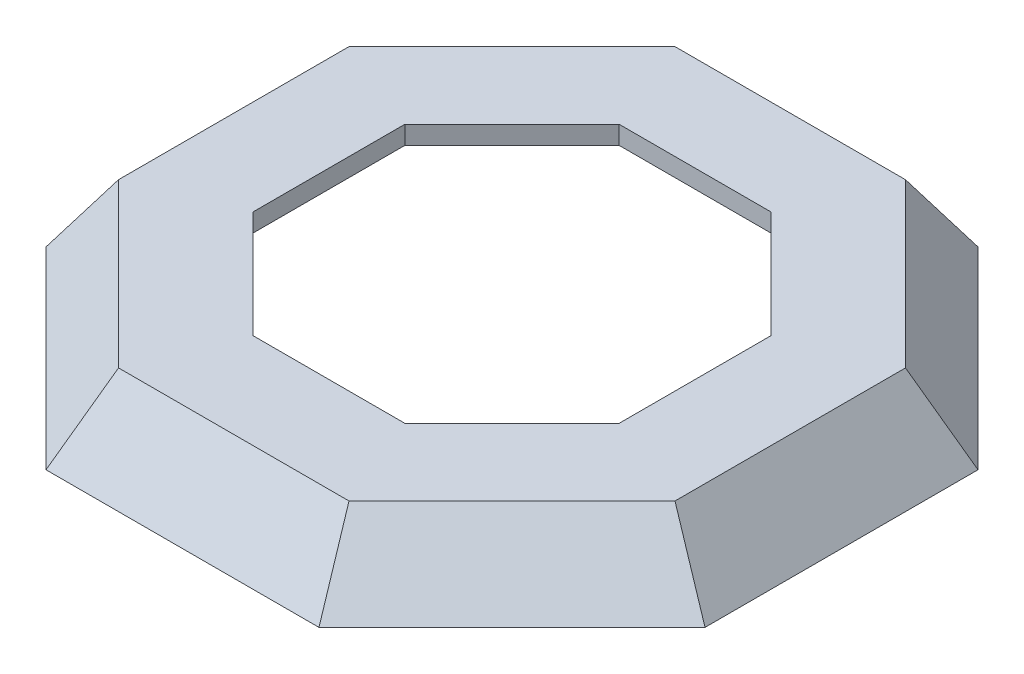
SolidWorks part; units mm, degrees
ref_plane "Front Plane" through (0, 0, 0) normal (0, 0, 1) x (1, 0, 0)
ref_plane "Top Plane" through (0, 0, 0) normal (0, 1, 0) x (1, 0, 0)
ref_plane "Right Plane" through (0, 0, 0) normal (1, 0, 0) x (0, 0, -1)
sketch "Sketch1" plane through (0, 0, 0) normal (0, 1, 0) x (1, 0, 0)
  line L1 (90, -37.2792) -> (90, 37.2792)
  line L2 (90, 37.2792) -> (37.2792, 90)
  line L3 (37.2792, 90) -> (-37.2792, 90)
  line L4 (-37.2792, 90) -> (-90, 37.2792)
  line L5 (-90, 37.2792) -> (-90, -37.2792)
  line L6 (-90, -37.2792) -> (-37.2792, -90)
  line L7 (-37.2792, -90) -> (37.2792, -90)
  line L8 (37.2792, -90) -> (90, -37.2792)
  circle A0 centre (0, 0) radius 90 construction
  dimension "D1" = 180
extrude "Boss-Extrude1" add sketch "Sketch1" along normal blind 20
chamfer "Chamfer1" distance 20 angle 35 8 edges at (0, 20, 90) (-63.6396, 20, 63.6396) (-90, 20, 0) (-63.6396, 20, -63.6396) (0, 20, -90) (63.6396, 20, -63.6396) (90, 20, 0) (63.6396, 20, 63.6396) first distance on face at (0, 10, 90) first distance on face at (-63.6396, 10, 63.6396) first distance on face at (-90, 10, 0) first distance on face at (-63.6396, 10, -63.6396) first distance on face at (0, 10, -90) first distance on face at (63.6396, 10, -63.6396) first distance on face at (90, 10, 0) first distance on face at (63.6396, 10, 63.6396)
shell "Shell1" thickness 5 removed face at (0, 0, 0)
sketch "Sketch2" plane through (0, 20, 0) normal (0, 1, 0) x (1, 0, 0)
  line L1 (20.7107, 50) -> (-20.7107, 50)
  line L2 (-20.7107, 50) -> (-50, 20.7107)
  line L3 (-50, 20.7107) -> (-50, -20.7107)
  line L4 (-50, -20.7107) -> (-20.7107, -50)
  line L5 (-20.7107, -50) -> (20.7107, -50)
  line L6 (20.7107, -50) -> (50, -20.7107)
  line L7 (50, -20.7107) -> (50, 20.7107)
  line L8 (50, 20.7107) -> (20.7107, 50)
  circle A0 centre (0, 0) radius 50 construction
  dimension "D1" = 100
extrude "Cut-Extrude2" cut sketch "Sketch2" against normal through all
